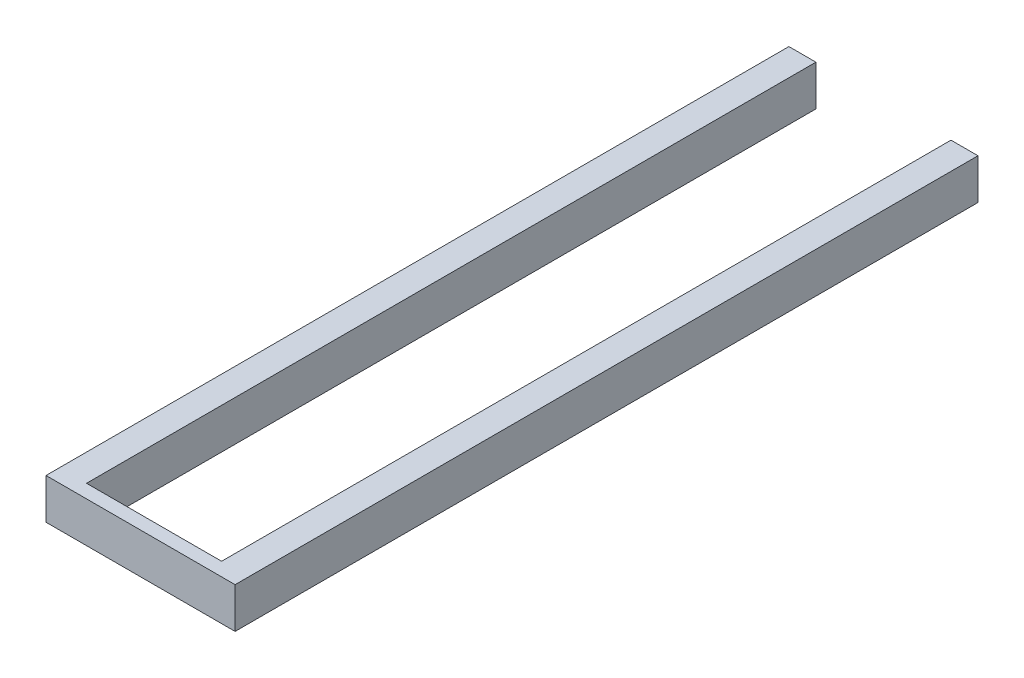
SolidWorks part; units mm, degrees
ref_plane "Front Plane" through (0, 0, 0) normal (0, 0, 1) x (1, 0, 0)
ref_plane "Top Plane" through (0, 0, 0) normal (0, 1, 0) x (1, 0, 0)
ref_plane "Right Plane" through (0, 0, 0) normal (1, 0, 0) x (0, 0, -1)
sketch "Sketch1" plane through (0, 0, 0) normal (0, 1, 0) x (1, 0, 0)
  line L0 (25, 135) -> (35, 135)
  line L2 (-25, 135) -> (-25, -135)
  line L3 (-25, -135) -> (25, -135)
  line L4 (25, 135) -> (25, -135)
  line L5 (-25, 135) -> (25, -135) construction
  line L6 (-25, -135) -> (25, 135) construction
  line L7 (35, 135) -> (35, -140)
  line L8 (35, -140) -> (-35, -140)
  line L9 (-35, -140) -> (-35, 135)
  line L10 (-35, 135) -> (-25, 135)
  point P0 (0, 0)
  dimension "D1" = 50
  dimension "D2" = 270
  dimension "D3" = 50
  dimension "D4" = 10
  dimension "D5" = 10
  dimension "D6" = 5
extrude "Boss-Extrude1" add sketch "Sketch1" along normal mid plane 15
